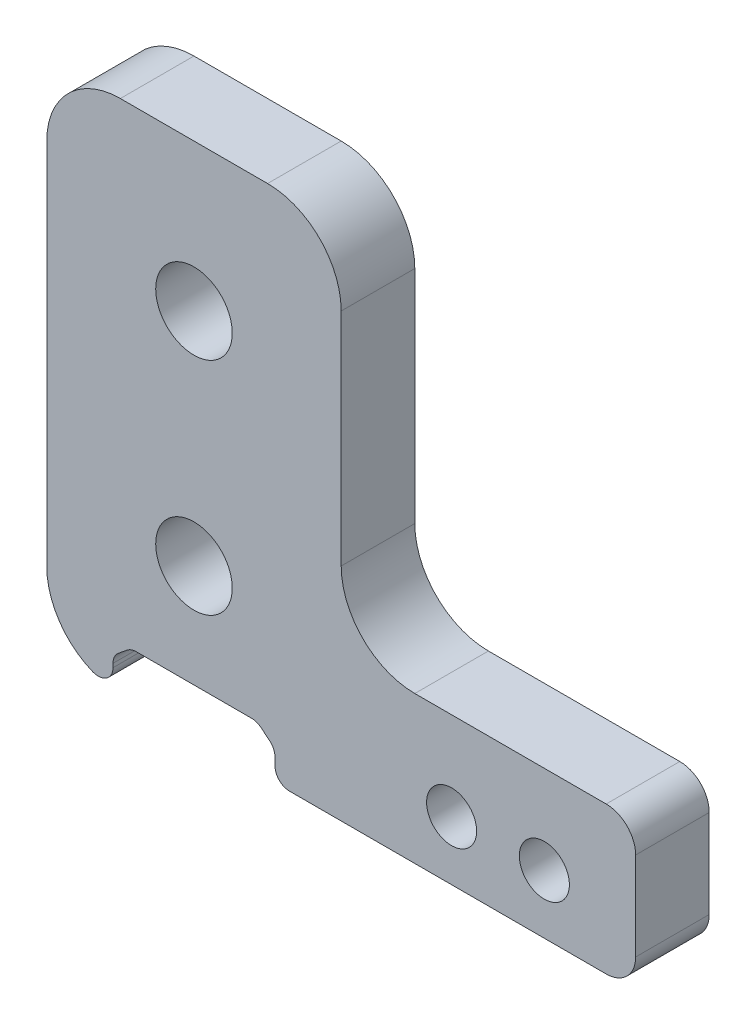
SolidWorks part; units mm, degrees
ref_plane "Front Plane" through (0, 0, 0) normal (0, 0, 1) x (1, 0, 0)
ref_plane "Top Plane" through (0, 0, 0) normal (0, 1, 0) x (1, 0, 0)
ref_plane "Right Plane" through (0, 0, 0) normal (1, 0, 0) x (0, 0, -1)
sketch "Sketch3" plane through (0, 0, 0) normal (0, 0, 1) x (1, 0, 0)
  line L0 (20, -35) -> (40, -35)
  line L1 (0, 0) -> (20, 0)
  line L2 (0, 0) -> (0, -35)
  line L3 (0, -35) -> (20, -35)
  line L4 (20, 0) -> (20, -25)
  line L5 (40, -35) -> (40, -25)
  line L6 (40, -25) -> (20, -25)
  line L7 (20, -25) -> (20, -35) construction
  dimension "D1" = 20
  dimension "D2" = 35
  dimension "D3" = 20
  dimension "D4" = 10
extrude "Boss-Extrude1" add sketch "Sketch3" along normal blind 5 contours L2 L3 L0 L5 L6 L4 L1
sketch "Sketch5" plane through (0, 0, 0) normal (0, 0, -1) x (-1, 0, 0)
  line L0 (-10, 0) -> (-10, -35) construction
  line L1 (0, 0) -> (-20, 0) construction
  line L2 (0, -35) -> (-40, -35) construction
  circle A0 centre (-10, -25) radius 2.6
  circle A1 centre (-10, -10) radius 2.6
  dimension "D2" = 5.2
  dimension "D1" = 15
  dimension "D3" = 10
extrude "Cut-Extrude1" cut sketch "Sketch5" against normal blind 5 contours L0 A1 | A1 L0 | A0 region at (8.8965, -10, 0) region at (11.1035, -10, 0)
sketch "Sketch6" plane through (0, 0, 0) normal (0, 0, -1) x (-1, 0, 0)
  line L0 (-27.5, -31) -> (-33.8, -31) construction
  line L1 (0, -35) -> (-40, -35) construction
  line L3 (-20, 0) -> (-20, -25) construction
  circle A0 centre (-27.5, -31) radius 1.7
  circle A1 centre (-33.8, -31) radius 1.7
  point P3 (-30.65, -31)
  dimension "D2" = 3.4
  dimension "D1" = 6.3
  dimension "D3" = 4
  dimension "D4" = 7.5
extrude "Cut-Extrude2" cut sketch "Sketch6" against normal up to next
sketch "Sketch8" plane through (0, 0, 0) normal (0, 0, -1) x (-1, 0, 0)
  line L0 (-4.5, -35) -> (-4.5, -33)
  line L1 (0, -35) -> (-40, -35) construction
  line L2 (-15.5, -35) -> (-15.5, -33)
  line L3 (-10, -10) -> (-10, -25) construction
  line L4 (-4.5, -33) -> (-5.7264, -32)
  line L5 (-5.7264, -32) -> (-14.2736, -32)
  line L6 (-14.2736, -32) -> (-15.5, -33)
  line L7 (-4.5, -35) -> (-15.5, -35)
  point P6 (-10, -32)
  point P9 (-10, -35)
  dimension "D1" = 11
  dimension "D2" = 2
  dimension "D3" = 1
extrude "Cut-Extrude4" cut sketch "Sketch8" against normal up to next contours L5 L6 L2 L7 L0 L4
fillet "Fillet4" radius 1 5 edges at (15.5, -33, 2.5) (14.2736, -32, 2.5) (5.7264, -32, 2.5) (4.5, -33, 2.5) (15.5, -35, 2.5)
fillet "Fillet1" radius 5 4 edges at (20, -25, 2.5) (0, -35, 2.5) (0, 0, 2.5) (20, 0, 2.5)
fillet "Fillet2" radius 2 2 edges at (40, -35, 2.5) (40, -25, 2.5)
fillet "Fillet5" radius 1 1 edges at (4.5, -35, 2.5)
